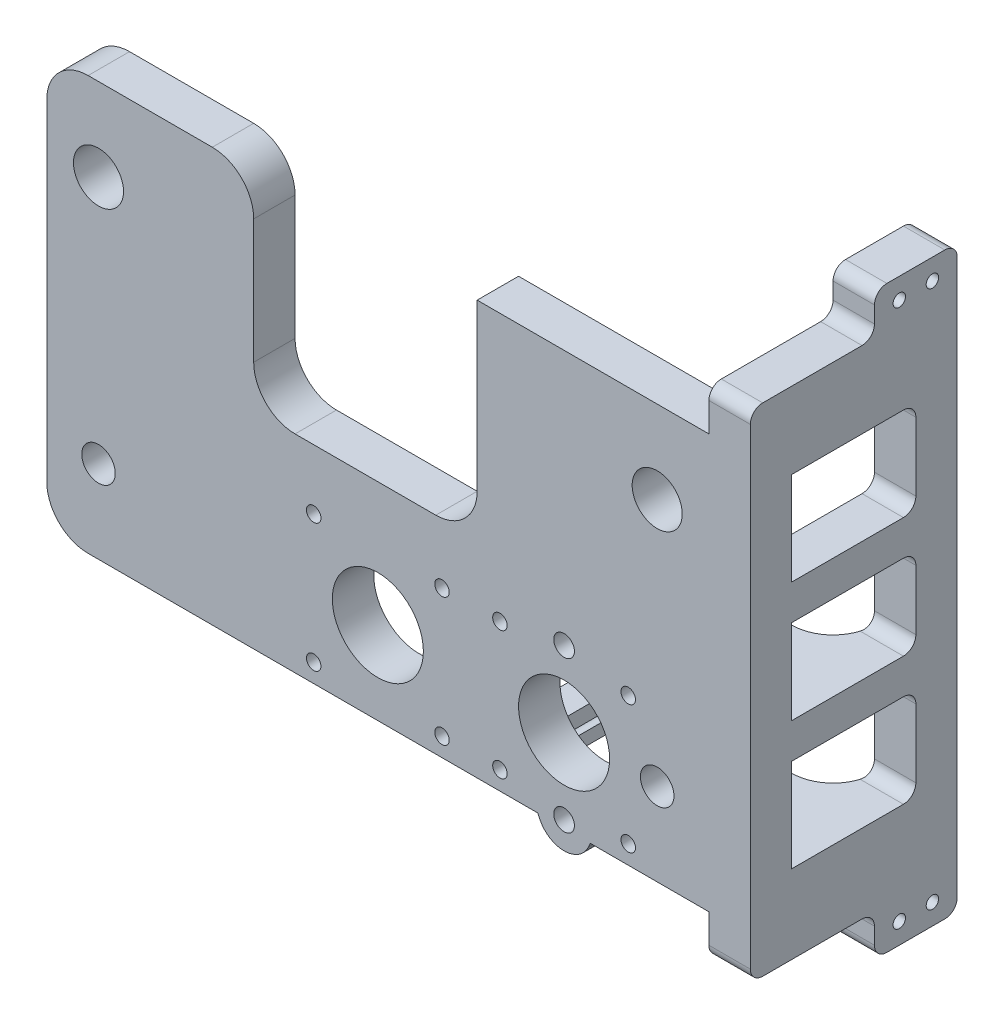
SolidWorks part; units mm, degrees
ref_plane "Front Plane" through (0, 0, 0) normal (0, 0, 1) x (1, 0, 0)
ref_plane "Top Plane" through (0, 0, 0) normal (0, 1, 0) x (1, 0, 0)
ref_plane "Right Plane" through (0, 0, 0) normal (1, 0, 0) x (0, 0, -1)
sketch "Sketch1" plane through (0, 0, 0) normal (0, 0, 1) x (1, 0, 0)
  line L0 (-67.5, 0) -> (67.5, 0) construction
  line L1 (80, 20) -> (42.5, 20)
  line L2 (80, 20) -> (80, -80)
  line L3 (80, -80) -> (51.3559, -80)
  line L4 (-80, 20) -> (-80, -80)
  line L5 (42.5, -18.25) -> (42.5, 18.25) construction
  line L6 (45, -78.25) -> (45, -41.75) construction
  line L7 (-15.5, -15.5) -> (15.5, -15.5) construction
  line L8 (-15.5, -15.5) -> (-15.5, 15.5) construction
  line L9 (-15.5, 15.5) -> (15.5, 15.5) construction
  line L10 (15.5, -15.5) -> (15.5, 15.5) construction
  line L11 (-15.5, -15.5) -> (15.5, 15.5) construction
  line L12 (-15.5, 15.5) -> (15.5, -15.5) construction
  line L13 (-30, 20) -> (-30, -30)
  line L14 (-67.5, -60) -> (67.5, -60) construction
  line L15 (-67.5, -60) -> (-67.5, 0) construction
  line L16 (-67.5, 0) -> (67.5, 0) construction
  line L17 (67.5, -60) -> (67.5, 0) construction
  line L20 (-30, -30) -> (24, -30)
  line L21 (24, -30) -> (24, 20)
  line L22 (0, -111.2369) -> (0, 89.7732) construction
  line L23 (-30, 20) -> (-80, 20)
  line L24 (39.109, -80.997) -> (38.6441, -80)
  line L25 (50.891, -80.997) -> (51.3559, -80)
  line L26 (38.6441, -80) -> (-80, -80)
  line L27 (42.5, 20) -> (24, 20)
  line L28 (24, -30) -> (24, -80) construction
  circle A0 centre (-67.5, 0) radius 6.05
  circle A1 centre (67.5, 0) radius 6.05
  circle A2 centre (67.5, -60) radius 4.05
  circle A3 centre (-67.5, -60) radius 4.05
  circle A4 centre (0, 0) radius 11 construction
  circle A5 centre (15.5, 15.5) radius 1.75 construction
  circle A6 centre (-15.5, 15.5) radius 1.75 construction
  circle A7 centre (-15.5, -15.5) radius 1.75 construction
  circle A8 centre (15.5, -15.5) radius 1.75 construction
  circle A11 centre (-15.5, -44.5) radius 1.75
  circle A12 centre (15.5, -44.5) radius 1.75
  circle A13 centre (0, -60) radius 11
  circle A14 centre (-15.5, -75.5) radius 1.75
  circle A15 centre (15.5, -75.5) radius 1.75
  circle A21 centre (60.5, -44.5) radius 1.75
  circle A22 centre (29.5, -44.5) radius 1.75
  circle A23 centre (45, -60) radius 11
  circle A24 centre (60.5, -75.5) radius 1.75
  circle A25 centre (29.5, -75.5) radius 1.75
  circle A32 centre (45, -41.75) radius 2.5
  circle A33 centre (45, -78.25) radius 2.5
  arc A36 (39.109, -80.997) -> (50.891, -80.997) centre (45, -78.25) ccw
  point P0 (0, 0)
  point P16 (0, 0)
  point P32 (0, 0)
  point P71 (45, -60)
  dimension "D3" = 12.1
  dimension "D4" = 2
  dimension "D5" = 30
  dimension "D6" = 50
  dimension "D7" = 20
  dimension "D8" = 22
  dimension "D10" = 3.5
  dimension "D11" = 20
  dimension "D13" = 36.5
  dimension "D14" = 36.5
  dimension "D16" = 5
  dimension "D18" = 24
  dimension "D20" = 13
  dimension "D24" = 8.1
  dimension "D2" = 100
  dimension "D9" = 31
  dimension "D15" = 80
  dimension "D22" = 310
  dimension "D23" = 160
  dimension "D17" = 2
extrude "Boss-Extrude1" add sketch "Sketch1" along normal blind 10
sketch "Sketch3" plane through (0, 0, 10) normal (0, 0, 1) x (1, 0, 0)
  circle A0 centre (67.5, 0) radius 6
  circle A1 centre (67.5, 0) radius 6.05
  circle A2 centre (67.5, 0) radius 6.05 construction
  circle A3 centre (-67.5, 0) radius 6.05
  circle A4 centre (-67.5, 0) radius 10
  circle A5 centre (67.5, 0) radius 10
  circle A8 centre (-67.5, 0) radius 6.05 construction
  circle A9 centre (-67.5, -60) radius 7
  circle A10 centre (-67.5, -60) radius 4.05
  circle A11 centre (-67.5, -60) radius 4.05 construction
  circle A12 centre (67.5, -60) radius 7
  circle A13 centre (67.5, -60) radius 4.05
  circle A14 centre (67.5, -60) radius 4.05 construction
  circle M11 centre (-67.5, 0) radius 6.05
  circle M12 centre (67.5, 0) radius 6.05
  circle M13 centre (67.5, -60) radius 4.05
  circle M14 centre (-67.5, -60) radius 4.05
  dimension "D1" = 12
  dimension "D2" = 12.1
  dimension "D3" = 20
  dimension "D4" = 12.1
  dimension "D5" = 8.1
  dimension "D6" = 14
  dimension "D7" = 8.1
  dimension "D8" = 14
extrude "Boss-Extrude3" add sketch "Sketch3" against normal blind 20 contours A12 M13 | A5 M12 | A9 M14 | A4 M11 region at (-77.2172, 0, 10) region at (57.7828, 0, 10) region at (-74.302, -60, 10) region at (60.698, -60, 10)
sketch "Sketch4" plane through (80, 0, 0) normal (1, 0, 0) x (0, 0, -1)
  line L0 (-10, -80) -> (-10, 20) construction
  line L1 (40, -90) -> (-10, -90)
  line L2 (40, -90) -> (40, 30)
  line L3 (40, 30) -> (-10, 30)
  line L4 (-10, -90) -> (-10, 30)
  point P5 (-10, -30)
  point P6 (-10, -30)
  dimension "D1" = 120
  dimension "D2" = 50
extrude "Boss-Extrude4" add sketch "Sketch4" along normal blind 10
sketch "Sketch5" plane through (0, 0, 0) normal (0, 0, -1) x (-1, 0, 0)
  line L9 (-24, -40) -> (-24, -48.5)
  line L10 (-24, -40) -> (-80, -40)
  line L11 (-80, -40) -> (-80, -48.5)
  line L12 (-24, -48.5) -> (-80, -48.5)
  line L13 (-24, -71) -> (-24, -79.5)
  line L14 (-24, -79.5) -> (-80, -79.5)
  line L15 (-80, -71) -> (-80, -79.5)
  line L16 (-24, -71) -> (-80, -71)
extrude "Boss-Extrude5" add sketch "Sketch5" along normal blind 20
sketch "Sketch6" plane through (0, 0, -40) normal (0, 0, -1) x (-1, 0, 0)
  line L20 (-80, -90) -> (-80, 30)
  line L37 (-80, 30) -> (-90, 30)
  line L38 (-90, 30) -> (-90, -90)
  line L39 (-90, -90) -> (-80, -90)
  line L40 (-80, -90) -> (-80, 30)
  line L57 (-80, 30) -> (-90, 30)
  line L58 (-90, 30) -> (-90, -90)
  line L59 (-90, -90) -> (-80, -90)
  circle A0 centre (-29.5, -75.5) radius 1.75 construction
  circle A1 centre (-60.5, -75.5) radius 1.75 construction
  circle A2 centre (-60.5, -44.5) radius 1.75 construction
  circle A3 centre (-29.5, -44.5) radius 1.75 construction
  circle A8 centre (-29.5, -75.5) radius 1.75
  circle A9 centre (-60.5, -75.5) radius 1.75
  circle A10 centre (-60.5, -44.5) radius 1.75
  circle A11 centre (-29.5, -44.5) radius 1.75
  dimension "D1" = 0
extrude "Cut-Extrude2" cut sketch "Sketch6" against normal up to surface (50 mm away) contours A10 | A11 | A9 | A8 up to face at (47.5, -41.75, 10)
sketch "Sketch7" plane through (0, 20, 0) normal (0, 1, 0) x (1, 0, 0)
  line L0 (31, 0) -> (54, 0)
  line L1 (31, 0) -> (31, 15.7654)
  line L2 (31, 15.7654) -> (54, 15.7654)
  line L3 (54, 15.7654) -> (54, 0)
  line L4 (24, -10) -> (24, 0) construction
  dimension "D1" = 7
  dimension "D2" = 23
extrude "Cut-Extrude3" cut sketch "Sketch7" against normal through all
sketch "Sketch8" plane through (0, -80, 0) normal (0, -1, 0) x (1, 0, 0)
  line L1 (24, -20) -> (24, 0) construction
  line L8 (56.5, 0) -> (33.5, 0)
  line L9 (56.5, -15.7654) -> (56.5, 0)
  line L10 (33.5, -15.7654) -> (56.5, -15.7654)
  line L11 (33.5, 0) -> (33.5, -15.7654)
  dimension "D2" = 23
  dimension "D1" = 9.5
extrude "Cut-Extrude9" cut sketch "Sketch8" against normal up to surface (40 mm away) up to face at (47.25, -40, -8.9413)
sketch "Sketch10" plane through (90, 0, 0) normal (1, 0, 0) x (0, 0, -1)
  line L0 (40, 30) -> (-10, 30) construction
  line L1 (30, 11.5) -> (0, 11.5)
  line L2 (30, 11.5) -> (30, -11)
  line L3 (30, -11) -> (0, -11)
  line L4 (0, 11.5) -> (0, -11)
  line L5 (30, -48.5) -> (0, -48.5)
  line L6 (30, -48.5) -> (30, -71)
  line L7 (30, -71) -> (0, -71)
  line L8 (0, -48.5) -> (0, -71)
  line L9 (40, -90) -> (40, 30) construction
  line L10 (-10, 30) -> (-10, -90) construction
  line L12 (30, -19.5) -> (0, -19.5)
  line L13 (30, -19.5) -> (30, -40)
  line L14 (30, -40) -> (0, -40)
  line L15 (0, -19.5) -> (0, -40)
  dimension "D1" = 18.5
  dimension "D2" = 22.5
  dimension "D3" = 78.5
  dimension "D4" = 22.5
  dimension "D5" = 10
  dimension "D6" = 10
  dimension "D7" = 8.5
  dimension "D8" = 8.5
extrude "Cut-Extrude10" cut sketch "Sketch10" against normal blind 10
sketch "Sketch11" plane through (0, 30, 0) normal (0, 1, 0) x (1, 0, 0)
  line L0 (80, 40) -> (80, -10) construction
  line L1 (80, 20) -> (90, 20)
  line L2 (80, 20) -> (80, 40)
  line L3 (80, 40) -> (90, 40)
  line L4 (90, 20) -> (90, 40)
  dimension "D1" = 20
extrude "Boss-Extrude6" add sketch "Sketch11" along normal blind 10
sketch "Sketch12" plane through (0, -90, 0) normal (0, -1, 0) x (1, 0, 0)
  line L4 (90, -20) -> (80, -20)
  line L5 (90, -40) -> (90, -20)
  line L6 (80, -40) -> (90, -40)
  line L7 (80, -20) -> (80, -40)
  line L8 (90, -20) -> (80, -20)
  line L9 (90, -40) -> (90, -20)
  line L10 (80, -40) -> (90, -40)
  line L11 (80, -20) -> (80, -40)
  dimension "D1" = 0
extrude "Boss-Extrude7" add sketch "Sketch12" along normal blind 10
fillet "Fillet1" radius 3 18 edges at (56.5, -75.25, 0) (56.5, -44.25, 0) (56.5, -75.25, -15.7654) (56.5, -44.25, -15.7654) (85, -11, -30) (85, -40, -30) (85, -71, -30) (85, -48.5, -30) (85, -19.5, -30) (85, 11.5, -30) (85, 40, -20) (85, 40, -40) (85, -100, -20) (85, -100, -40) (85, -90, 10) (85, 30, 10) (85, -90, -20) (85, 30, -20)
fillet "Fillet2" radius 10 7 edges at (-30, 20, 5) (-80, 20, 5) (-80, -80, 5) (24, -30, 5) (-30, -30, 5) (80, -44.25, -20) (80, -75.25, -20)
sketch "Sketch13" plane through (90, 0, 0) normal (1, 0, 0) x (0, 0, -1)
  line L0 (40, -97) -> (40, 37) construction
  line L1 (23, 40) -> (37, 40) construction
  circle A0 centre (34, 35) radius 1.5
  circle A2 centre (26, 35) radius 1.5
  circle A3 centre (26, -95) radius 1.5
  circle A4 centre (34, -95) radius 1.5
  dimension "D1" = 3
  dimension "D2" = 8
  dimension "D3" = 6
  dimension "D4" = 5
  dimension "D5" = 2
extrude "Cut-Extrude11" cut sketch "Sketch13" against normal blind 10
